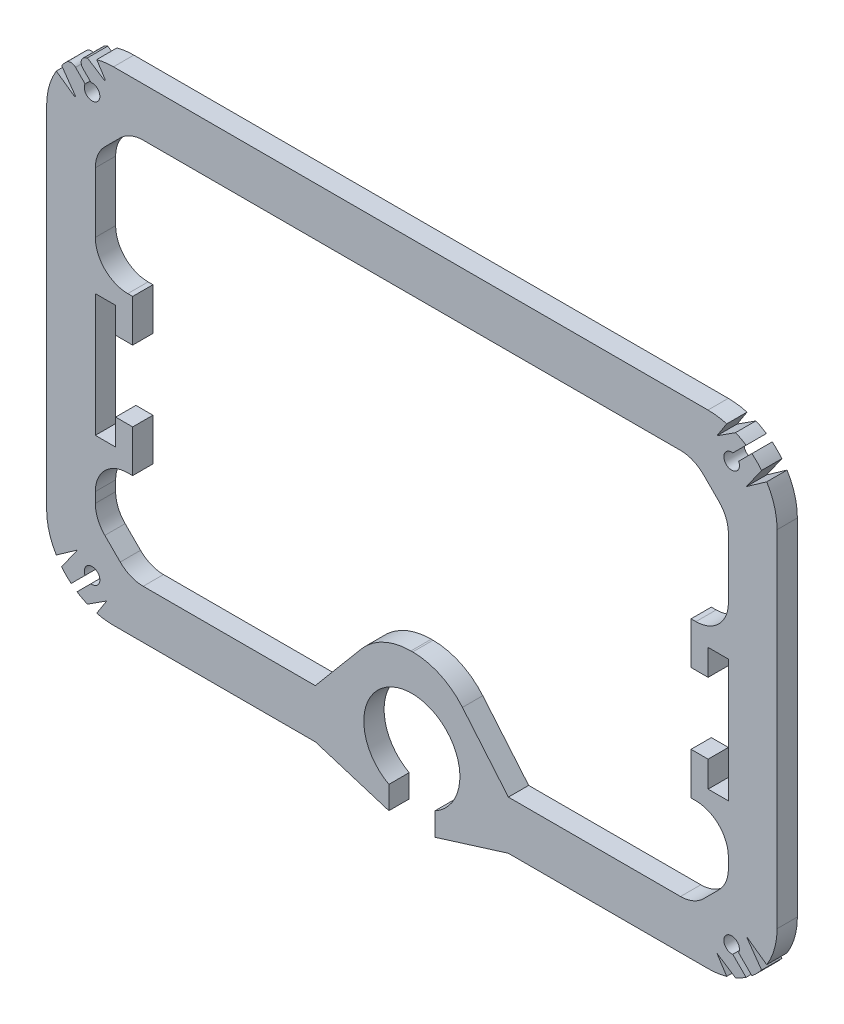
SolidWorks part; units mm, degrees
material "Delrin 2700 NC010, Low Viscosity Acetal Copolymer (SS)"
ref_plane "Front Plane" through (0, 0, 0) normal (0, 0, 1) x (1, 0, 0)
ref_plane "Top Plane" through (0, 0, 0) normal (0, 1, 0) x (1, 0, 0)
ref_plane "Right Plane" through (0, 0, 0) normal (1, 0, 0) x (0, 0, -1)
sketch "Sketch1" plane through (0, 0, 0) normal (0, 0, 1) x (1, 0, 0)
  line L0 (-23.3423, -18.923) -> (-7.5425, -18.923)
  line L1 (-24.765, 13.6903) -> (-24.765, -13.6903)
  line L2 (-23.3423, -15.113) -> (-7.5521, -15.113)
  line L3 (7.5521, -15.113) -> (23.1704, -15.113)
  line L4 (24.765, 13.5184) -> (24.765, -13.5184)
  line L5 (-1000, 0) -> (49000, 0) construction
  line L6 (-1.7968, -18.923) -> (-1.7968, -20.7107)
  line L7 (7.5425, -18.923) -> (23.1704, -18.923)
  line L8 (23.1704, 15.113) -> (-23.3423, 15.113)
  line L9 (-7.5521, -15.113) -> (-3.9596, -10.8316)
  line L10 (-28.575, 13.6903) -> (-28.575, -13.6903)
  line L11 (7.5521, -15.113) -> (3.9596, -10.8316)
  line L12 (-0.0681, -9.017) -> (0.0681, -9.017)
  line L13 (28.575, 13.5184) -> (28.575, -13.5184)
  line L14 (23.1704, 18.923) -> (-23.3423, 18.923)
  line L15 (1.7968, -18.923) -> (1.7968, -20.7107)
  line L16 (-7.5425, -18.923) -> (-1.7968, -20.7107)
  line L17 (7.5425, -18.923) -> (1.7968, -20.7107)
  line L18 (0, 12.5532) -> (0, -24.2768) construction
  line L19 (1.7968, -18.923) -> (23.1704, -18.923) construction
  line L20 (-23.3423, -18.923) -> (-1.7968, -18.923) construction
  line L21 (-24.765, 5.0849) -> (0, 5.0849) construction
  line L22 (0, 5.0849) -> (24.765, 5.0849) construction
  arc A0 (1.7968, -18.923) -> (-1.7968, -18.923) centre (0, -15.621) ccw
  arc A1 (-23.3423, -15.113) -> (-24.765, -13.6903) centre (-23.3423, -13.6903) cw
  arc A2 (-0.0681, -9.017) -> (-3.9596, -10.8316) centre (-0.0681, -14.097) ccw
  arc A3 (24.765, -13.5184) -> (23.1704, -15.113) centre (23.1704, -13.5184) cw
  arc A4 (23.1704, 15.113) -> (24.765, 13.5184) centre (23.1704, 13.5184) cw
  arc A5 (-23.3423, -18.923) -> (-28.575, -13.6903) centre (-23.3423, -13.6903) cw
  arc A6 (28.575, -13.5184) -> (23.1704, -18.923) centre (23.1704, -13.5184) cw
  arc A7 (23.1704, 18.923) -> (28.575, 13.5184) centre (23.1704, 13.5184) cw
  arc A8 (-23.3423, 18.923) -> (-28.575, 13.6903) centre (-23.3423, 13.6903) ccw
  circle A9 centre (-25.019, 16.383) radius 0.6096
  circle A10 centre (25.019, 16.383) radius 0.6096
  arc A11 (-23.3423, 15.113) -> (-24.765, 13.6903) centre (-23.3423, 13.6903) ccw
  arc A12 (0.0681, -9.017) -> (3.9596, -10.8316) centre (0.0681, -14.097) cw
  circle A13 centre (25.019, -16.383) radius 0.6096
  circle A14 centre (-25.019, -16.383) radius 0.6096
  circle A15 centre (0, -15.621) radius 5.3975 construction
  arc A18 (7.5521, -15.113) -> (-7.5521, -15.113) centre (0, -15.621) ccw construction
  point P0 (0, 0)
  dimension "D4" = 3.302
  dimension "D6" = 37.846
  dimension "D7" = 3.556
  dimension "D8" = 3.81
  dimension "D9" = 6.604
  dimension "D5" = 1.2192
  dimension "D2" = 49.53
  dimension "D3" = 7.5184
  dimension "D10" = 5.08
  dimension "D11" = 5.08
  dimension "D14" = 10.795
  dimension "D12" = 2.54
extrude "Boss-Extrude1" add sketch "Sketch1" along normal blind 1.5875
sketch "Sketch2" plane through (-24.765, 0, 0) normal (1, 0, 0) x (0, 0, -1)
  line L0 (0, 2.8448) -> (-1.5875, 2.8448)
  line L1 (0, -6.7596) -> (-1.5875, -6.7596) construction
  line L2 (-1.5875, -15.113) -> (0, -15.113)
  line L3 (-1.5875, -15.113) -> (0, -15.113) construction
  line L4 (0, -13.6903) -> (0, 13.6903)
  line L5 (0, 13.6903) -> (-1.5875, 13.6903)
  line L6 (-1.5875, 13.6903) -> (-1.5875, -13.6903)
  line L7 (0, 13.6903) -> (-1.5875, 13.6903)
  line L8 (0, -13.6903) -> (0, 4.1148)
  line L9 (-1.5875, -15.113) -> (-1.5875, -8.0296)
  line L10 (-1.5875, 4.1148) -> (-1.5875, -13.6903)
  line L11 (-1.5875, -13.6903) -> (0, -13.6903)
  line L12 (0, -15.113) -> (0, -8.0296)
  line L13 (0, 4.1148) -> (-1.5875, 4.1148)
  line L14 (-1.5875, 2.8448) -> (-1.5875, -6.6447)
  line L15 (-1.5875, 4.1148) -> (-1.5875, 2.8448)
  line L16 (0, 2.8448) -> (0, 4.1148)
  line L17 (0, -7.9147) -> (0, 1.4693)
  line L18 (-1.5875, -7.9147) -> (-1.5875, -6.6447)
  line L19 (0, -6.7596) -> (-1.5875, -6.7596)
  line L21 (0, -8.0296) -> (-1.5875, -8.0296)
  line L22 (0, -8.0296) -> (0, -13.6903)
  line L23 (-1.5875, -8.0296) -> (-1.5875, -13.6903)
  line L24 (47.9467, 2.8448) -> (1.4151, 2.8448) construction
  line L28 (-1.5875, -13.6903) -> (0, -13.6903)
  line L29 (47.5608, -9.6909) -> (1.4354, -6.848) construction
  line M5 (0, -13.6903) -> (0, 13.6903)
  line M7 (-1.5875, 13.6903) -> (-1.5875, -13.6903)
  dimension "D1" = 0
  dimension "D2" = 1.27
  dimension "D4" = 1.27
extrude "Boss-Extrude2" add sketch "Sketch2" along normal blind 2.921 contours L13 L10 L0 M5 | L19 L17 L8 L0 L10 M7 | L21 L8 L19 L18 M5 M7 region at (-24.765, -1.9574, 0.7937) region at (-24.765, 3.4798, 0.7937) region at (-24.765, -7.3946, 0.7937)
extrude "Cut-Extrude1" cut sketch "Sketch2<3>" along normal blind 1.5875 contours L19 L17 L0 M5 M7 region at (-24.765, -1.9574, 0.7937)
sketch "Sketch2<3>" plane through (-24.765, 0, 0) normal (1, 0, 0) x (0, 0, -1) same geometry as "Sketch2"
sketch "Sketch3" plane through (-23.1775, 0, 0) normal (-1, 0, 0) x (0, 0, 1)
  line L0 (0, 2.8448) -> (1.5875, 2.8448) construction
  line L1 (0, -6.7596) -> (1.5875, -6.7596) construction
  line L2 (0, 2.8448) -> (1.5875, 2.8448)
  line L3 (0, -6.7596) -> (1.5875, -6.7596)
  line L4 (0, 0.8128) -> (1.5875, 0.8128)
  line L5 (0, -4.7276) -> (1.5875, -4.7276)
  line L6 (1.5875, 0.8128) -> (1.5875, -4.7276)
  line L7 (0, -4.7276) -> (0, 0.8128)
  line M2 (1.5875, -6.7596) -> (1.5875, 2.8448)
  line M4 (0, 2.8448) -> (0, -6.7596)
  dimension "D1" = 2.032
  dimension "D2" = 2.032
extrude "Cut-Extrude2" cut sketch "Sketch3" against normal up to surface (1.3335 mm away) contours L5 L4 M4 M2 region at (-23.1775, -1.9574, 0.7937) up to face at (-21.844, -1.9574, 0.7937)
mirror "Mirror1" about plane through (0, 0, 0) normal (1, 0, 0) of "Cut-Extrude2", "Boss-Extrude2", "Cut-Extrude1"
fillet "Fillet5" radius 2.54 4 edges at (24.765, 4.1148, 0.7937) (24.765, -8.0296, 0.7937) (-24.765, -8.0296, 0.7937) (-24.765, 4.1148, 0.7937)
sketch "Sketch4" plane through (0, 0, 1.5875) normal (0, 0, 1) x (1, 0, 0)
  line L0 (-26.1985, 18.0748) -> (-25.1096, 16.9858)
  line L1 (-26.6549, 17.7409) -> (-25.566, 16.652)
  line L2 (23.1704, 18.923) -> (-23.3423, 18.923) construction
  circle A0 centre (-25.019, 16.383) radius 0.6096 construction
  arc A1 (-23.3423, 18.923) -> (-28.575, 13.6903) centre (-23.3423, 13.6903) ccw construction
  arc A2 (-26.1985, 18.0748) -> (-26.6549, 17.7409) centre (-23.3423, 13.6903) ccw
  arc A3 (-25.1096, 16.9858) -> (-25.566, 16.652) centre (-25.019, 16.383) ccw
  dimension "SnapInSlot" = 0.5588
  dimension "D2" = 45
extrude "Slot for installing carbon rod" cut sketch "Sketch4" against normal through all
sketch "Sketch7" plane through (0, 0, 1.5875) normal (0, 0, 1) x (1, 0, 0)
  line L1 (-25.3841, 18.5082) -> (-25.1147, 18.7776)
  line L2 (-24.8453, 19.047) -> (-23.8695, 17.5325)
  line L3 (-25.019, 16.383) -> (-25.4501, 15.9519) construction
  line L4 (-25.3841, 18.5082) -> (-23.8695, 17.5325)
  line L5 (-27.817, 19.2981) -> (-21.1897, 12.6708) construction
  line L6 (-23.8695, 17.5325) -> (-27.139, 20.8019) construction
  line L7 (-25.1096, 16.9858) -> (-26.1985, 18.0748) construction
  line L8 (-25.1147, 18.7776) -> (-24.8453, 19.047)
  line L9 (-26.6549, 17.7409) -> (-25.566, 16.652) construction
  line L10 (-25.4501, 15.9519) -> (-26.1685, 15.2335) construction
  line L11 (-26.1685, 15.2335) -> (-29.8887, 18.9538) construction
  line L12 (-27.7224, 16.7874) -> (-27.453, 17.0568)
  line L13 (-27.453, 17.0568) -> (-26.1685, 15.2335)
  line L14 (-26.1685, 15.2335) -> (-27.9918, 16.518)
  line L15 (-25.019, 16.383) -> (-24.5879, 16.8141) construction
  line L16 (-24.5879, 16.8141) -> (-23.8695, 17.5325) construction
  line L17 (23.1704, 15.113) -> (-23.3423, 15.113) construction
  line L18 (-27.9918, 16.518) -> (-27.7224, 16.7874)
  line L19 (-24.765, 13.6903) -> (-24.765, 6.6548) construction
  arc A0 (-25.566, 16.652) -> (-25.1096, 16.9858) centre (-25.019, 16.383) ccw construction
  arc A3 (-23.3423, 18.923) -> (-26.1985, 18.0748) centre (-23.3423, 13.6903) ccw construction
  dimension "D1" = 0.762
  dimension "D2" = 45
  dimension "D3" = 1.016
  dimension "D4" = 1.016
  dimension "D5" = 0.762
  dimension "D6" = 45
extrude "Bending slot" cut sketch "Sketch7" against normal through all
fillet "Fillet10" radius 0.0508 2 edges at (-26.1685, 15.2335, 0.7937) (-23.8695, 17.5325, 0.7937)
fillet "Fillet8" radius 0.508 2 edges at (-26.6549, 17.7409, 0.7937) (-26.1985, 18.0748, 0.7937)
sketch "Sketch5" plane through (0, 0, 1.5875) normal (0, 0, 1) x (1, 0, 0)
  line L0 (-24.765, 12.4203) -> (-22.0723, 15.113)
  line L1 (-24.765, 13.6903) -> (-24.765, 6.6548) construction
  line L2 (23.1704, 15.113) -> (-23.3423, 15.113) construction
  line L3 (-22.0723, 15.113) -> (-23.3423, 15.113)
  line L4 (-24.765, 13.6903) -> (-24.765, 12.4203)
  arc A0 (-23.3423, 15.113) -> (-24.765, 13.6903) centre (-23.3423, 13.6903) ccw construction
  arc A1 (-23.3423, 15.113) -> (-24.765, 13.6903) centre (-23.3423, 13.6903) ccw
  dimension "D1" = 1.27
extrude "Boss-Extrude3" add sketch "Sketch5" against normal up to surface (1.5875 mm away) up to face at (-0.0065, -2.9492, 0)
mirror "Mirror2" about plane through (0, 0, 0) normal (1, 0, 0) of "Bending slot", "Slot for installing carbon rod", "Boss-Extrude3"
mirror "Mirror4" about plane through (0, 0, 0) normal (0, 1, 0) of "Boss-Extrude3", "Mirror2"
fillet "Fillet7" radius 2.54 8 edges at (22.0723, -15.113, 0.7937) (24.765, -12.4203, 0.7937) (-22.0723, -15.113, 0.7937) (-24.765, -12.4203, 0.7937) (24.765, 12.4203, 0.7937) (22.0723, 15.113, 0.7937) (-22.0723, 15.113, 0.7937) (-24.765, 12.4203, 0.7937)
